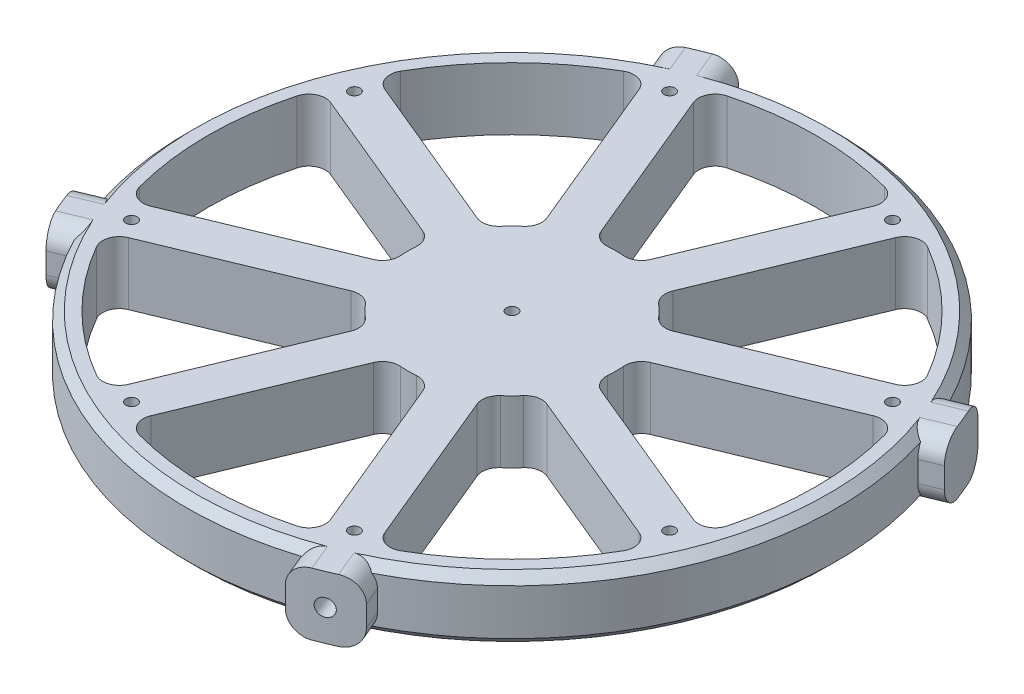
SolidWorks part; units mm, degrees
ref_plane "Front Plane" through (0, 0, 0) normal (0, 0, 1) x (1, 0, 0)
ref_plane "Top Plane" through (0, 0, 0) normal (0, 1, 0) x (1, 0, 0)
ref_plane "Right Plane" through (0, 0, 0) normal (1, 0, 0) x (0, 0, -1)
sketch "Sketch2" plane through (0, 0, 0) normal (1, 0, 0) x (0, 0, -1)
  line L0 (0, 0) -> (-78.0999, 0)
  line L1 (-78.0999, 0) -> (-78.0999, 15)
  line L2 (-78.0999, 15) -> (0, 15)
  line L5 (0, 15) -> (0, 0)
  dimension "D1" = 78.0999
  dimension "D2" = 15
ref_axis "Axis1" through (0, -1.0952, 0) along (0, 1, 0)
revolve "Revolve1" add sketch "Sketch2" angle 360 about axis through (0, -1.0952, 0) along (0, 1, 0)
hole_wizard "#6-32 Tapped Hole2" positions "Sketch6" profile "Sketch7" tap size "#6-32" standard "ANSI Inch" end condition through all
sketch "Sketch6" plane through (0, 15, 0) normal (0, 1, 0) x (1, 0, 0)
  line L0 (0, 0) -> (-53.438, 129.0108) construction
  line L2 (0, 0) -> (0, 109.0908) construction
  point P0 (-26.7878, 64.6716)
  dimension "D1" = 22.5
  dimension "D2" = 70
sketch "Sketch7" plane through (-26.7878, 15, -64.6716) normal (1, 0, 0) x (0, 0, 1)
  line L0 (0, 0) -> (0, 15)
  line L1 (0, 15) -> (1.3525, 15)
  line L2 (1.3525, 15) -> (1.3525, 0)
  line L5 (1.3525, 0) -> (0, 0)
  line L11 (0, -6.35) -> (0, 107.95) construction
  dimension "Thread Major Dia." = 2.7051
  dimension "Thru Tap Drill Depth" = 15
pattern_circular "CirPattern3" count 8 over 360 about axis through (0, -1.0952, 0) along (0, 1, 0) of "#6-32 Tapped Hole2"
sketch "Sketch8" plane through (0, 15, 0) normal (0, 1, 0) x (1, 0, 0)
  line L4 (0, 0) -> (0, 93.9995) construction
  line L5 (0, 0) -> (113.8372, 0) construction
  line L6 (-4.7544, 24.5438) -> (-23.2892, 69.2908)
  line L7 (4.7544, 24.5438) -> (23.2892, 69.2908)
  line L8 (0, 0) -> (-26.7878, 64.6716) construction
  arc A0 (-4.7544, 24.5438) -> (4.7544, 24.5438) centre (0, 0) cw
  arc A1 (-23.2892, 69.2908) -> (23.2892, 69.2908) centre (0, 0) cw
  circle A2 centre (0, 0) radius 78.0999 construction
  dimension "D1" = 25
  dimension "D2" = 5
  dimension "D3" = 5
extrude "Cut-Extrude1" cut sketch "Sketch8" against normal through all
fillet "Fillet1" radius 4 4 edges at (4.7544, 7.5, -24.5438) (23.2892, 7.5, -69.2908) (-4.7544, 7.5, -24.5438) (-23.2892, 7.5, -69.2908)
pattern_circular "CirPattern4" count 8 over 360 about axis through (0, -1.0952, 0) along (0, 1, 0) of "Cut-Extrude1", "Fillet1"
hole_wizard "#6-32 Tapped Hole1" positions "Sketch9" profile "Sketch11" tap size "#6-32" standard "ANSI Inch" end condition through all
sketch "Sketch9" plane through (0, 0, 0) normal (0, -1, 0) x (-1, 0, 0)
  point P0 (0, 0)
sketch "Sketch11" plane through (0, 0, 0) normal (1, 0, 0) x (0, 0, -1)
  line L0 (0, 0) -> (0, 15)
  line L1 (0, 15) -> (1.3525, 15)
  line L2 (1.3525, 15) -> (1.3525, 0)
  line L5 (1.3525, 0) -> (0, 0)
  line L11 (0, -6.35) -> (0, 107.95) construction
  dimension "Thru Tap Drill Dia." = 2.7051
  dimension "Thru Tap Drill Depth" = 15
cosmetic thread "Hole Thread1" parameters "D2"=3.5052
sketch "Sketch12" plane through (0, 15, 0) normal (0, 1, 0) x (1, 0, 0)
  line L0 (0, 0) -> (-26.7878, 64.6716) construction
  line L1 (-22.8683, 74.6769) -> (-24.7435, 79.2039)
  line L2 (-38.5093, 73.5019) -> (-36.6342, 68.9749)
  circle A0 centre (0, 0) radius 78.0999 construction
  arc A1 (-24.7435, 79.2039) -> (-38.5093, 73.5019) centre (0, 0) ccw
  circle A2 centre (0, 0) radius 78.0999 construction
  arc A3 (-36.6342, 68.9749) -> (-22.8683, 74.6769) centre (0, 0) cw
  dimension "D1" = 14.9
  dimension "D2" = 4.9
extrude "Boss-Extrude1" add sketch "Sketch12" against normal blind 15
fillet "Fillet2" radius 5 4 edges at (-23.8059, 15, -76.9404) (-37.5717, 15, -71.2384) (-23.8059, 0, -76.9404) (-37.5717, 0, -71.2384)
pattern_circular "CirPattern5" count 4 over 360 about axis through (0, -1.0952, 0) along (0, 1, 0) of "Fillet2", "Boss-Extrude1"
chamfer "Chamfer1" distance 2 angle 45 8 edges at (72.1549, 0, 29.8875) (-29.8875, 0, 72.1549) (-72.1549, 0, -29.8875) (-72.1549, 15, -29.8875) (-29.8875, 15, 72.1549) (72.1549, 15, 29.8875) (29.8875, 0, -72.1549) (29.8875, 15, -72.1549)
ref_plane "Plane1" through (0, 0, 0) normal (0.3827, 0, 0.9239) x (0, 1, 0)
hole_wizard "#20 (0.161) Diameter Hole1" positions "Sketch16" profile "Sketch15" hole size "#20" standard "ANSI Inch" end condition through all
sketch "Sketch16" plane through (0, 0, 0) normal (0.3827, 0, 0.9239) x (0, 1, 0)
  point P0 (7.5, 0)
  dimension "D1" = 7.5
sketch "Sketch15" plane through (0, 7.5, 0) normal (0, 1, 0) x (-0.9239, 0, 0.3827)
  line L0 (0, 0) -> (0, 103.8553)
  line L1 (0, 103.8553) -> (2.0447, 103.8553)
  line L2 (2.0447, 103.8553) -> (2.0447, 0)
  line L5 (2.0447, 0) -> (0, 0)
  line L11 (0, -6.35) -> (0, 107.95) construction
  dimension "Thru Hole Dia." = 4.0894
  dimension "Thru Hole Depth" = 103.8553
equation "\"TubeDiameter\" = 6.5433in"
equation "\"D1@Sketch2\"=(\"TubeDiameter\"/2)-5mm"
